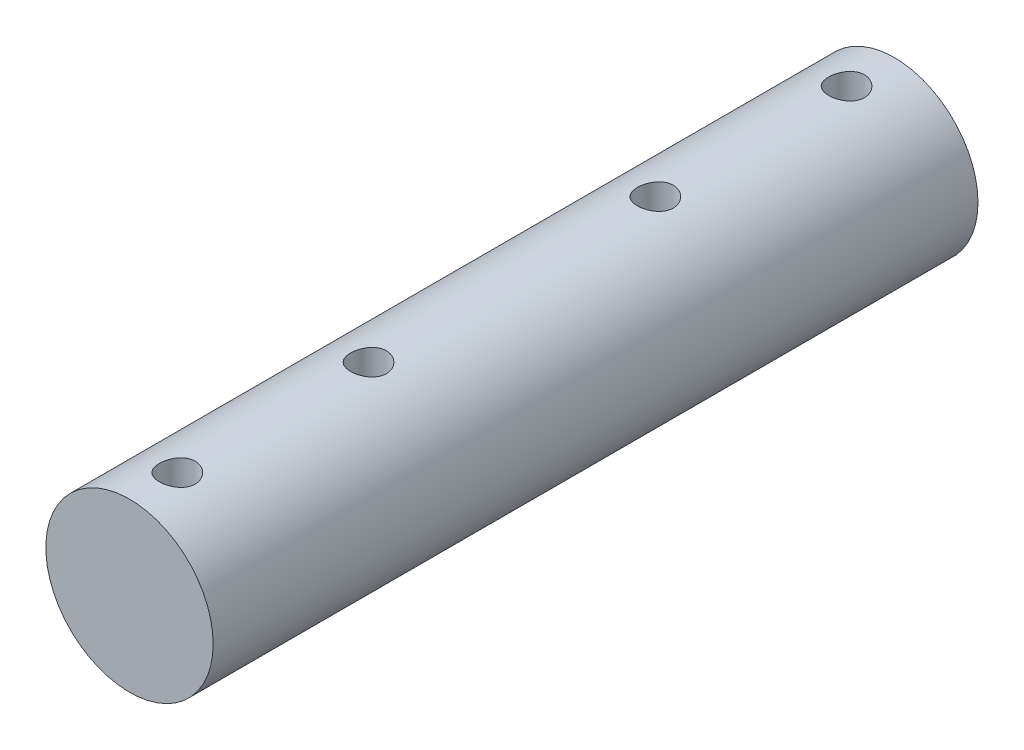
SolidWorks part; units mm, degrees
material "6063-O, Extruded Rod (SS)"
ref_plane "Front Plane" through (0, 0, 0) normal (0, 0, 1) x (1, 0, 0)
ref_plane "Top Plane" through (0, 0, 0) normal (0, 1, 0) x (1, 0, 0)
ref_plane "Right Plane" through (0, 0, 0) normal (1, 0, 0) x (0, 0, -1)
sketch "Sketch1" plane through (0, 0, 0) normal (0, 0, 1) x (1, 0, 0)
  circle A0 centre (0, 0) radius 22.225
  dimension "D1" = 44.45
extrude "Boss-Extrude1" add sketch "Sketch1" along normal blind 203.2
sketch "Sketch2" plane through (0, 0, 0) normal (0, 1, 0) x (1, 0, 0)
  line L0 (-22.225, -203.2) -> (22.225, -203.2) construction
  line L1 (22.225, 0) -> (-22.225, 0) construction
  circle A0 centre (0, -190.5) radius 4.7625
  circle A1 centre (0, -139.7) radius 4.7625
  circle A2 centre (0, -12.7) radius 4.7625
  circle A3 centre (0, -63.5) radius 4.7625
  dimension "D1" = 76.2
  dimension "D2" = 50.8
  dimension "D3" = 50.8
  dimension "D4" = 12.7
  dimension "D5" = 12.7
  dimension "D6" = 9.525
  dimension "D7" = 9.525
  dimension "D8" = 9.525
  dimension "D9" = 9.525
extrude "Cut-Extrude1" cut sketch "Sketch2" against normal blind 203.2 and the other way blind 203.2
